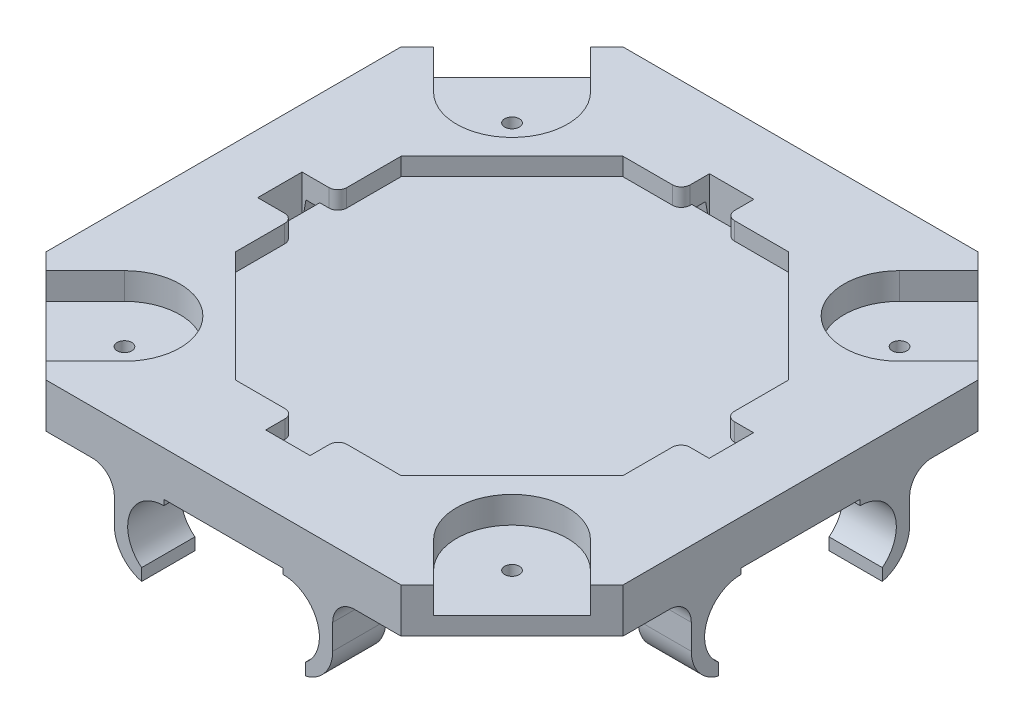
SolidWorks part; units mm, degrees
ref_plane "Front Plane" through (0, 0, 0) normal (0, 0, 1) x (1, 0, 0)
ref_plane "Top Plane" through (0, 0, 0) normal (0, 1, 0) x (1, 0, 0)
ref_plane "Right Plane" through (0, 0, 0) normal (1, 0, 0) x (0, 0, -1)
sketch "Sketch2" plane through (0, 0, 0) normal (0, 1, 0) x (1, 0, 0)
  line L0 (-1040, 738.75) -> (-1015, 763.75)
  line L1 (-1015, 763.75) -> (-935, 763.75)
  line L2 (-1040, 738.75) -> (-1040, 658.75)
  line L3 (-1015, 633.75) -> (-935, 633.75)
  line L4 (-910, 738.75) -> (-910, 658.75)
  line L5 (-1040, 658.75) -> (-1015, 633.75)
  line L6 (-935, 633.75) -> (-910, 658.75)
  line L7 (-935, 763.75) -> (-910, 738.75)
extrude "Boss-Extrude2" add sketch "Sketch2" along normal blind 10
sketch "Sketch3" plane through (0, 10, 0) normal (0, 1, 0) x (1, 0, 0)
  line L0 (-1036.3372, 655.0872) -> (-1027.4984, 663.926)
  line L1 (-1040, 658.75) -> (-1015, 633.75) construction
  line L2 (-922.4984, 646.2516) -> (-931.3372, 637.4128)
  line L3 (-1009.8207, 646.2484) -> (-1018.6595, 637.4095)
  line L4 (-1018.6595, 637.4095) -> (-1036.3372, 655.0872)
  line L5 (-1036.3372, 742.4128) -> (-1027.4984, 733.574)
  line L6 (-1015, 763.75) -> (-1040, 738.75) construction
  line L8 (-1009.8207, 751.2516) -> (-1018.6595, 760.0905)
  line L9 (-1018.6595, 760.0905) -> (-1036.3372, 742.4128)
  line L10 (-913.6595, 655.0905) -> (-922.4984, 663.9293)
  line L11 (-935, 633.75) -> (-910, 658.75) construction
  line L13 (-940.176, 646.2516) -> (-931.3372, 637.4128)
  line L14 (-922.4984, 646.2516) -> (-913.6595, 655.0905)
  line L15 (-913.6595, 742.4095) -> (-922.4984, 733.5707)
  line L16 (-910, 738.75) -> (-935, 763.75) construction
  line L18 (-940.176, 751.2484) -> (-931.3372, 760.0872)
  line L19 (-931.3372, 760.0872) -> (-913.6595, 742.4095)
  arc A0 (-1009.8207, 646.2484) -> (-1027.4984, 663.926) centre (-1018.6595, 655.0872) ccw
  arc A1 (-922.4984, 663.9293) -> (-940.176, 646.2516) centre (-931.3372, 655.0905) ccw
  arc A2 (-940.176, 751.2484) -> (-922.4984, 733.5707) centre (-931.3372, 742.4095) ccw
  arc A3 (-1027.4984, 733.574) -> (-1009.8207, 751.2516) centre (-1018.6595, 742.4128) ccw
  dimension "D1" = 25
  dimension "D2" = 25
  dimension "D3" = 25
  dimension "D4" = 25
  dimension "D5" = 5.18
  dimension "D6" = 5.1753
  dimension "D7" = 5.18
  dimension "D8" = 5.18
  dimension "D9" = 5.18
extrude "Cut-Extrude1" cut sketch "Sketch3" against normal blind 6
sketch "Sketch4" plane through (0, 4, 0) normal (0, 1, 0) x (1, 0, 0)
  circle A0 centre (-1018.6595, 655.0872) radius 1.65
  circle A1 centre (-931.3372, 655.0905) radius 1.65
  circle A2 centre (-931.3372, 742.4095) radius 1.65
  circle A3 centre (-1018.6595, 742.4128) radius 1.65
  dimension "D1" = 3.3
  dimension "D2" = 3.3
  dimension "D3" = 3.3
  dimension "D4" = 3.3
extrude "Cut-Extrude2" cut sketch "Sketch4" against normal blind 6
sketch "Sketch5" plane through (0, 10, 0) normal (0, 1, 0) x (1, 0, 0)
  line L0 (-1040, 738.75) -> (-1040, 658.75) construction
  line L1 (-1040, 724.75) -> (-910, 724.75)
  line L2 (-1040, 724.75) -> (-1040, 672.75)
  line L3 (-1040, 672.75) -> (-910, 672.75)
  line L4 (-910, 724.75) -> (-910, 672.75)
  line L5 (-910, 658.75) -> (-910, 738.75) construction
  dimension "D1" = 52
  dimension "D2" = 14
  dimension "D3" = 14
extrude "Cut-Extrude3" cut sketch "Sketch5" against normal blind 4
sketch "Sketch6" plane through (0, 0, 0) normal (0, -1, 0) x (-1, 0, 0)
  line L0 (935, 763.75) -> (1015, 763.75) construction
  line L1 (1003.6595, 653.75) -> (988.6595, 653.75)
  line L2 (1003.6595, 653.75) -> (1003.6595, 668.75)
  line L3 (1003.6595, 743.75) -> (988.6595, 743.75)
  line L4 (988.6595, 653.75) -> (988.6595, 668.75)
  line L5 (1015, 633.75) -> (935, 633.75) construction
  line L6 (910, 658.75) -> (910, 738.75) construction
  line L7 (961.3372, 743.75) -> (946.3372, 743.75)
  line L8 (961.3372, 743.75) -> (961.3372, 728.75)
  line L9 (961.3372, 653.75) -> (946.3372, 653.75)
  line L10 (946.3372, 743.75) -> (946.3372, 728.75)
  line L11 (1020, 681.25) -> (1003.6595, 681.25)
  line L12 (1020, 681.25) -> (1020, 668.75)
  line L13 (1020, 668.75) -> (1003.6595, 668.75)
  line L14 (930, 681.25) -> (930, 668.75)
  line L15 (988.6595, 716.25) -> (961.3372, 716.25)
  line L16 (1020, 728.75) -> (1003.6595, 728.75)
  line L17 (1020, 728.75) -> (1020, 716.25)
  line L18 (1020, 716.25) -> (1003.6595, 716.25)
  line L19 (930, 728.75) -> (930, 716.25)
  line L20 (1003.6595, 728.75) -> (1003.6595, 743.75)
  line L21 (988.6595, 728.75) -> (961.3372, 728.75)
  line L22 (988.6595, 728.75) -> (988.6595, 743.75)
  line L23 (961.3372, 716.25) -> (961.3372, 681.25)
  line L24 (946.3372, 728.75) -> (930, 728.75)
  line L25 (946.3372, 716.25) -> (946.3372, 681.25)
  line L26 (946.3372, 716.25) -> (930, 716.25)
  line L27 (946.3372, 681.25) -> (930, 681.25)
  line L28 (946.3372, 668.75) -> (930, 668.75)
  line L29 (946.3372, 668.75) -> (946.3372, 653.75)
  line L30 (961.3372, 668.75) -> (961.3372, 653.75)
  line L31 (988.6595, 681.25) -> (961.3372, 681.25)
  line L32 (988.6595, 681.25) -> (988.6595, 716.25)
  line L33 (1003.6595, 681.25) -> (1003.6595, 716.25)
  line L34 (988.6595, 668.75) -> (961.3372, 668.75)
  circle A0 centre (1018.6595, 655.0872) radius 1.65 construction
  circle A1 centre (931.3372, 655.0905) radius 1.65 construction
  dimension "D1" = 90
  dimension "D2" = 20
  dimension "D3" = 20
  dimension "D4" = 15
  dimension "D5" = 15
  dimension "D6" = 15
  dimension "D7" = 15
  dimension "D8" = 90
  dimension "D9" = 20
  dimension "D10" = 12.5
  dimension "D11" = 35
  dimension "D12" = 12.5
  dimension "D13" = 35
extrude "Boss-Extrude3" add sketch "Sketch6" along normal blind 6 draft 33
sketch "Sketch7" plane through (0, 10, 0) normal (0, 1, 0) x (1, 0, 0)
  line L3 (-1040, 672.75) -> (-910, 672.75)
  line L4 (-1040, 672.75) -> (-1040, 724.75)
  line L5 (-1040, 724.75) -> (-910, 724.75)
  line L6 (-910, 672.75) -> (-910, 724.75)
extrude "Boss-Extrude4" add sketch "Sketch7" against normal up to surface (4 mm away) up to face at (-975, 6, -698.75)
sketch "Sketch12" plane through (0, 0, -633.75) normal (0, 0, 1) x (1, 0, 0)
  line L0 (-1015, 0) -> (-935, 0) construction
  line L1 (-999.6, 0) -> (-996.6, 0)
  line L2 (-999.6, 0) -> (-999.6, -18.8)
  line L3 (-999.6, -18.8) -> (-996.6, -18.8)
  line L5 (-988.45, -1.25) -> (-988.45, 0)
  line L6 (-950.4, 0) -> (-953.4, 0)
  line L7 (-950.4, 0) -> (-950.4, -18.8)
  line L8 (-950.4, -18.8) -> (-953.4, -18.8)
  line L10 (-988.45, 0) -> (-996.6, 0)
  line L12 (-988.45, -18.8) -> (-996.6, -18.8)
  line L13 (-953.4, -18.8) -> (-961.55, -18.8)
  line L15 (-961.55, -1.25) -> (-961.55, 0)
  line L16 (-961.55, 0) -> (-953.4, 0)
  line L17 (-988.45, -18.8) -> (-984.45, -18.8)
  line L18 (-984.45, -18.8) -> (-984.45, -16.5009)
  line L19 (-961.55, -18.8) -> (-965.55, -18.8)
  line L20 (-965.55, -18.8) -> (-965.55, -16.5009)
  arc A0 (-988.45, -1.25) -> (-984.45, -16.5009) centre (-988.45, -9.4) ccw
  arc A1 (-965.55, -16.5009) -> (-961.55, -1.25) centre (-961.55, -9.4) ccw
  dimension "D8" = 16.3
  dimension "D9" = 16.3
  dimension "D1" = 18.8
  dimension "D2" = 18.8
  dimension "D3" = 3
  dimension "D4" = 3
  dimension "D5" = 43.2
  dimension "D6" = 15.4
  dimension "D7" = 15.4
  dimension "D10" = 4
  dimension "D11" = 4
extrude "Boss-Extrude5" add sketch "Sketch12" against normal blind 12
sketch "Sketch13" plane through (0, 0, -763.75) normal (0, 0, -1) x (-1, 0, 0)
  line L0 (961.3372, 0) -> (946.3372, 0) construction
  line L1 (950.4, 0) -> (953.4, 0)
  line L2 (950.4, 0) -> (950.4, -18.8)
  line L3 (950.4, -18.8) -> (953.4, -18.8)
  line L5 (950.4, -18.8) -> (950.4, 0) construction
  line L6 (965.55, -18.8) -> (950.4, -18.8) construction
  line L7 (1003.6595, 0) -> (988.6595, 0) construction
  line L8 (999.6, -18.8) -> (996.6, -18.8)
  line L9 (999.6, -18.8) -> (999.6, 0)
  line L10 (999.6, 0) -> (996.6, 0)
  line L12 (961.55, -1.25) -> (961.55, 0)
  line L13 (988.6595, 0) -> (961.3372, 0) construction
  line L14 (961.55, 0) -> (953.4, 0)
  line L15 (965.55, -16.5009) -> (965.55, -18.8)
  line L16 (965.55, -18.8) -> (953.4, -18.8)
  line L17 (988.45, -1.25) -> (988.45, 0)
  line L18 (988.45, 0) -> (996.6, 0)
  line L19 (984.45, -16.5009) -> (984.45, -18.8)
  line L20 (984.45, -18.8) -> (996.6, -18.8)
  arc A0 (961.55, -1.25) -> (965.55, -16.5009) centre (961.55, -9.4) ccw
  arc A1 (984.45, -16.5009) -> (988.45, -1.25) centre (988.45, -9.4) ccw
  dimension "D1" = 3
  dimension "D2" = 3
extrude "Boss-Extrude6" add sketch "Sketch13" against normal blind 12
sketch "Sketch14" plane through (-910, 0, 0) normal (1, 0, 0) x (0, 0, -1)
  line L0 (681.25, 0) -> (668.75, 0) construction
  line L1 (674.15, 0) -> (677.15, 0)
  line L2 (674.15, 0) -> (674.15, -18.8)
  line L3 (674.15, -18.8) -> (677.15, -18.8)
  line L5 (658.75, 0) -> (738.75, 0) construction
  line L6 (720.35, 0) -> (723.35, 0)
  line L8 (720.35, -18.8) -> (723.35, -18.8)
  line L9 (723.35, 0) -> (723.35, -18.8)
  line L10 (685.3, -18.8) -> (688.3, -18.8)
  line L11 (677.15, -18.8) -> (685.3, -18.8)
  line L12 (688.3, -18.8) -> (688.3, -16.9778)
  line L13 (685.3, -1.25) -> (685.3, 0)
  line L14 (716.25, 0) -> (681.25, 0) construction
  line L15 (677.15, 0) -> (685.3, 0)
  line L16 (720.35, -18.8) -> (709.2, -18.8)
  line L17 (709.2, -18.8) -> (709.2, -16.9778)
  line L18 (712.2, -1.25) -> (712.2, 0)
  line L19 (712.2, 0) -> (720.35, 0)
  arc A0 (685.3, -1.25) -> (688.3, -16.9778) centre (685.3, -9.4) ccw
  arc A1 (709.2, -16.9778) -> (712.2, -1.25) centre (712.2, -9.4) ccw
  dimension "D8" = 16.3
  dimension "D9" = 16.3
  dimension "D1" = 3
  dimension "D2" = 3
  dimension "D3" = 43.2
  dimension "D4" = 15.4
  dimension "D5" = 15.4
  dimension "D6" = 18.8
  dimension "D7" = 18.8
  dimension "D10" = 3
  dimension "D11" = 3
  dimension "D12" = 3
  dimension "D13" = 11.15
extrude "Boss-Extrude7" add sketch "Sketch14" against normal blind 12
sketch "Sketch15" plane through (-1040, 0, 0) normal (-1, 0, 0) x (0, 0, 1)
  line L0 (-723.35, -18.8) -> (-723.35, 0)
  line L1 (-738.75, 0) -> (-658.75, 0) construction
  line L2 (-716.25, 0) -> (-728.75, 0) construction
  line L3 (-723.35, -18.8) -> (-709.2, -18.8)
  line L4 (-709.2, -18.8) -> (-709.2, -16.9778)
  line L5 (-688.3, -16.9778) -> (-688.3, -18.8)
  line L6 (-688.3, -18.8) -> (-674.15, -18.8)
  line L7 (-674.15, -18.8) -> (-674.15, 0)
  line L8 (-668.75, 0) -> (-681.25, 0) construction
  line L9 (-712.2, -1.25) -> (-712.2, 0)
  line L10 (-681.25, 0) -> (-716.25, 0) construction
  line L11 (-712.2, 0) -> (-723.35, 0)
  line L12 (-685.3, -1.25) -> (-685.3, 0)
  line L13 (-685.3, 0) -> (-674.15, 0)
  arc A0 (-712.2, -1.25) -> (-709.2, -16.9778) centre (-712.2, -9.4) ccw
  arc A1 (-688.3, -16.9778) -> (-685.3, -1.25) centre (-685.3, -9.4) ccw
extrude "Boss-Extrude8" add sketch "Sketch15" against normal blind 12
fillet "Fillet2" radius 8.15 8 edges at (-999.6, -18.8, -757.75) (-950.4, -18.8, -757.75) (-916, -18.8, -723.35) (-916, -18.8, -674.15) (-950.4, -18.8, -639.75) (-999.6, -18.8, -639.75) (-1034, -18.8, -674.15) (-1034, -18.8, -723.35)
fillet "Fillet3" radius 5 8 edges at (-916, 0, -674.15) (-916, 0, -723.35) (-950.4, 0, -757.75) (-950.4, 0, -639.75) (-999.6, 0, -639.75) (-1034, 0, -674.15) (-1034, 0, -723.35) (-999.6, 0, -757.75)
sketch "Sketch16" plane through (0, 0, 0) normal (0, -1, 0) x (-1, 0, 0)
  line L0 (1028, 720.35) -> (1028, 709.2) construction
  line L1 (1026.7335, 670.15) -> (1022.7335, 670.15)
  line L2 (1026.7335, 670.15) -> (1026.7335, 721.775)
  line L3 (1026.7335, 721.775) -> (1022.7335, 721.775)
  line L4 (1022.7335, 670.15) -> (1022.7335, 721.775)
  line L5 (1003.525, 648.75) -> (947.475, 648.75)
  line L6 (1003.525, 648.75) -> (1003.525, 652.75)
  line L7 (1003.525, 652.75) -> (947.475, 652.75)
  line L8 (947.475, 648.75) -> (947.475, 652.75)
  line L9 (925, 670.15) -> (929, 670.15)
  line L10 (925, 670.15) -> (925, 726.275)
  line L11 (925, 726.275) -> (929, 726.275)
  line L12 (929, 670.15) -> (929, 726.275)
  line L13 (947.475, 748.75) -> (1003.6, 748.75)
  line L14 (947.475, 748.75) -> (947.475, 744.75)
  line L15 (947.475, 744.75) -> (1003.6, 744.75)
  line L16 (1003.6, 748.75) -> (1003.6, 744.75)
  line L17 (950.4, 751.75) -> (958.55, 751.75) construction
  line L18 (961.55, 763.75) -> (988.45, 763.75) construction
  line L19 (922, 715.2) -> (922, 723.35) construction
  line L20 (910, 682.3) -> (910, 674.15) construction
  line L21 (988.45, 645.75) -> (1004.6, 645.75) construction
  line L22 (958.55, 645.75) -> (950.4, 645.75) construction
  line L23 (1015, 633.75) -> (1004.6, 633.75) construction
  point P16 (1028, 714.775)
  point P22 (1028, 714.775)
  point P24 (954.475, 751.75)
  point P29 (922, 719.275)
  point P35 (996.525, 645.75)
  point P38 (954.475, 645.75)
  dimension "D1" = 7
  dimension "D2" = 4
  dimension "D3" = 7
  dimension "D4" = 7
  dimension "D5" = 7
  dimension "D6" = 4
  dimension "D7" = 15
  dimension "D8" = 7
  dimension "D9" = 7
  dimension "D10" = 15
  dimension "D11" = 4
  dimension "D12" = 4
  dimension "D13" = 7
  dimension "D14" = 7
  dimension "D15" = 19
extrude "Cut-Extrude7" cut sketch "Sketch16" against normal blind 5 draft 10
sketch "Sketch17" plane through (0, 0, -633.75) normal (0, 0, 1) x (1, 0, 0)
  line L1 (-991.45, -18.8) -> (-958.55, -18.8)
  line L2 (-991.45, -18.8) -> (-991.45, -13.1535)
  line L3 (-991.45, -13.1535) -> (-958.55, -13.1535)
  line L4 (-958.55, -18.8) -> (-958.55, -13.1535)
  dimension "D1" = 0
extrude "Cut-Extrude8" cut sketch "Sketch17" against normal blind 200
chamfer "Chamfer1" distance 1.5 angle 39 4 edges at (-958.55, -16.9778, -639.75) (-958.55, -16.9778, -757.75) (-991.45, -16.9778, -757.75) (-991.45, -16.9778, -639.75) first distance on face at (-956.7972, -8.4934, -639.75) first distance on face at (-956.7972, -8.4934, -757.75) first distance on face at (-993.2028, -8.4934, -757.75) first distance on face at (-993.2028, -8.4934, -639.75)
fillet "Fillet4" radius 2 4 edges at (-958.55, -18.8, -757.75) (-991.45, -18.8, -757.75) (-958.55, -18.8, -639.75) (-991.45, -18.8, -639.75)
sketch "Sketch18" plane through (0, 0, -633.75) normal (0, 0, 1) x (1, 0, 0)
  line L1 (-993.45, -15.836) -> (-956.55, -15.836)
  line L2 (-993.45, -15.836) -> (-993.45, -23.2539)
  line L3 (-993.45, -23.2539) -> (-956.55, -23.2539)
  line L4 (-956.55, -15.836) -> (-956.55, -23.2539)
  arc A0 (-988.45, -1.25) -> (-992.5013, -16.4717) centre (-988.45, -9.4) ccw construction
  arc A1 (-957.4987, -16.4717) -> (-961.55, -1.25) centre (-961.55, -9.4) ccw construction
  dimension "D1" = 5
  dimension "D2" = 5
extrude "Cut-Extrude9" cut sketch "Sketch18" against normal blind 200
sketch "Sketch19" plane through (-910, 0, 0) normal (1, 0, 0) x (0, 0, -1)
  line L1 (680.3, -22.0092) -> (717.2, -22.0092)
  line L2 (680.3, -22.0092) -> (680.3, -13.7585)
  line L3 (680.3, -13.7585) -> (717.2, -13.7585)
  line L4 (717.2, -22.0092) -> (717.2, -13.7585)
  arc A0 (685.3, -1.25) -> (688.3, -16.9778) centre (685.3, -9.4) ccw construction
  arc A1 (709.2, -16.9778) -> (712.2, -1.25) centre (712.2, -9.4) ccw construction
  dimension "D1" = 5
  dimension "D2" = 5
extrude "Cut-Extrude10" cut sketch "Sketch19" against normal blind 200
sketch "Sketch21" plane through (0, 0, 0) normal (0, -1, 0) x (-1, 0, 0)
  line L0 (1003.525, 652.75) -> (947.475, 652.75) construction
  line L1 (980.5, 652.75) -> (970.5, 652.75)
  line L2 (980.5, 652.75) -> (980.5, 648.75)
  line L3 (980.5, 648.75) -> (970.5, 648.75)
  line L4 (970.5, 652.75) -> (970.5, 648.75)
  line L5 (947.475, 648.75) -> (1003.525, 648.75) construction
  line L6 (929, 670.15) -> (929, 726.275) construction
  line L7 (929, 693.175) -> (925, 693.175)
  line L8 (929, 693.175) -> (929, 703.175)
  line L9 (929, 703.175) -> (925, 703.175)
  line L10 (925, 693.175) -> (925, 703.175)
  line L11 (925, 726.275) -> (925, 670.15) construction
  line L12 (1026.7335, 670.15) -> (1026.7335, 721.775) construction
  line L13 (1026.7335, 693.175) -> (1022.7335, 693.175)
  line L14 (1026.7335, 693.175) -> (1026.7335, 703.175)
  line L15 (1026.7335, 703.175) -> (1022.7335, 703.175)
  line L16 (1022.7335, 693.175) -> (1022.7335, 703.175)
  line L17 (1022.7335, 721.775) -> (1022.7335, 670.15) construction
  line L18 (1003.6, 748.75) -> (947.475, 748.75) construction
  line L19 (980.5, 748.75) -> (970.5, 748.75)
  line L20 (980.5, 748.75) -> (980.5, 744.75)
  line L21 (980.5, 744.75) -> (970.5, 744.75)
  line L22 (970.5, 748.75) -> (970.5, 744.75)
  line L23 (947.475, 744.75) -> (1003.6, 744.75) construction
  line L24 (947.475, 748.75) -> (947.475, 744.75) construction
  dimension "D1" = 10
  dimension "D2" = 23.025
  dimension "D3" = 23.025
  dimension "D4" = 23.025
  dimension "D5" = 10
  dimension "D6" = 10
  dimension "D7" = 23.025
  dimension "D8" = 10
  dimension "D9" = 23.025
extrude "Cut-Extrude11" cut sketch "Sketch21" against normal blind 200
sketch "Sketch22" plane through (0, 10, 0) normal (0, 1, 0) x (1, 0, 0)
  line L0 (-1018.6595, 717.4128) -> (-993.6595, 742.4128)
  line L1 (-993.6595, 742.4128) -> (-956.3372, 742.4128)
  line L2 (-1018.6595, 717.4128) -> (-1018.6595, 680.0905)
  line L3 (-993.6595, 655.0905) -> (-956.3372, 655.0905)
  line L4 (-931.3372, 717.4128) -> (-931.3372, 680.0905)
  line L6 (-956.3372, 742.4128) -> (-931.3372, 717.4128)
  line L8 (-931.3372, 680.0905) -> (-956.3372, 655.0905)
  line L10 (-993.6595, 655.0905) -> (-1018.6595, 680.0905)
extrude "Cut-Extrude12" cut sketch "Sketch22" against normal blind 4
sketch "Sketch23" plane through (0, 10, 0) normal (0, 1, 0) x (1, 0, 0)
  line L0 (-980.5, 693.175) -> (-980.5, 648.75)
  line L1 (-1026.7335, 693.175) -> (-980.5, 693.175)
  line L2 (-1026.7335, 693.175) -> (-1026.7335, 703.175)
  line L3 (-1026.7335, 703.175) -> (-980.5, 703.175)
  line L4 (-925, 693.175) -> (-925, 703.175)
  line L5 (-980.5, 748.75) -> (-970.5, 748.75)
  line L6 (-980.5, 748.75) -> (-980.5, 703.175)
  line L7 (-980.5, 648.75) -> (-970.5, 648.75)
  line L8 (-970.5, 748.75) -> (-970.5, 703.175)
  line L9 (-970.5, 703.175) -> (-925, 703.175)
  line L10 (-970.5, 693.175) -> (-925, 693.175)
  line L11 (-970.5, 693.175) -> (-970.5, 648.75)
extrude "Cut-Extrude13" cut sketch "Sketch23" against normal up to surface (4 mm away) up to face at (-974.9984, 6, -698.7516)
fillet "Fillet5" radius 2 8 edges at (-980.5, 8, -655.0905) (-970.5, 8, -655.0905) (-931.3372, 8, -693.175) (-931.3372, 8, -703.175) (-970.5, 8, -742.4128) (-980.5, 8, -742.4128) (-1018.6595, 8, -693.175) (-1018.6595, 8, -703.175)
